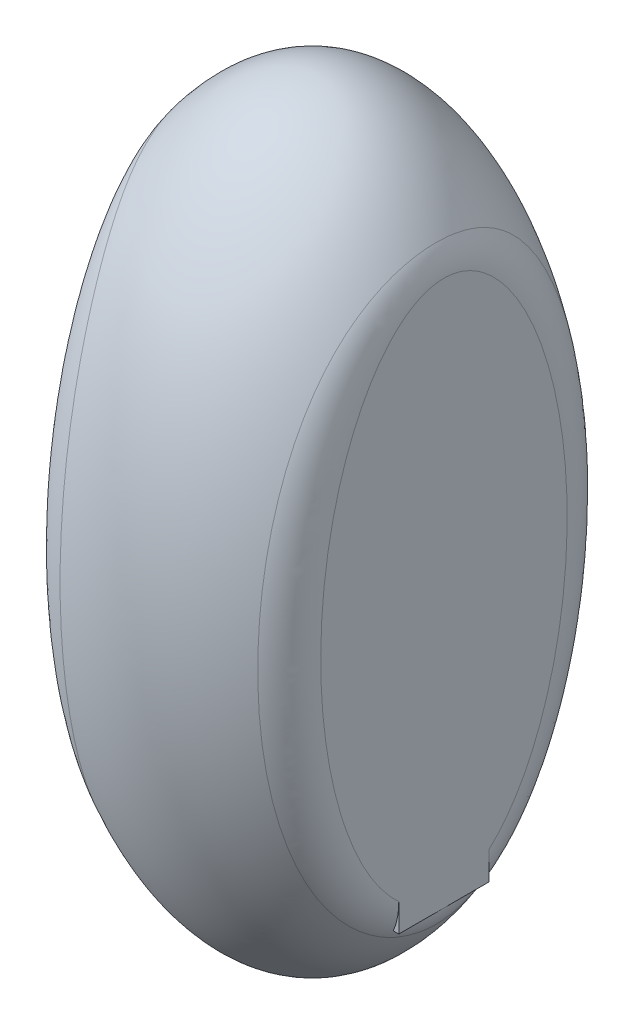
SolidWorks part; units mm, degrees
material "PBT General Purpose"
ref_plane "Front Plane" through (0, 0, 0) normal (0, 0, 1) x (1, 0, 0)
ref_plane "Top Plane" through (0, 0, 0) normal (0, 1, 0) x (1, 0, 0)
ref_plane "Right Plane" through (0, 0, 0) normal (1, 0, 0) x (0, 0, -1)
sketch "Sketch1" plane through (0, 0, 0) normal (0, 0, 1) x (1, 0, 0)
  line L0 (0, 1.15) -> (0, -1.15)
  ellipse E0 centre (0, 0) end of major axis (0, 1.15) minor radius 0.6 (0, -1.15) -> (0, 1.15) ccw
  dimension "D1" = 1.2
  dimension "D2" = 2.3
ref_axis "Axis1" through (0, 1.265, 0) along (0, -1, 0)
revolve "Revolve6" add sketch "Sketch1" angle 360 about L0
sketch "Sketch2" plane through (0, 0, 0) normal (0, 0, 1) x (1, 0, 0)
  line L0 (0, 1.265) -> (0, -1.265) construction
  line L1 (-0.4, 1.1771) -> (-0.895, 1.1771)
  line L2 (-0.4, 1.1771) -> (-0.4, -1.3571)
  line L3 (-0.4, -1.3571) -> (-0.895, -1.3571)
  line L4 (-0.895, 1.1771) -> (-0.895, -1.3571)
  line L5 (0.4, 1.1771) -> (1.03, 1.1771)
  line L6 (0.4, 1.1771) -> (0.4, -1.3571)
  line L7 (0.4, -1.3571) -> (1.03, -1.3571)
  line L8 (1.03, 1.1771) -> (1.03, -1.3571)
  dimension "D1" = 0.4
  dimension "D2" = 0.4
extrude "Cut-Extrude1" cut sketch "Sketch2" against normal through all both and the other way through all
fillet "Fillet1" radius 0.15 1 edges at (0.4, 0.851, -0.0533)
sketch "Sketch3" plane through (0.4, 0, 0) normal (1, 0, 0) x (0, 0, -1)
  line L0 (-0.1371, -0.7554) -> (-0.1371, -0.8413)
  line L1 (-0.1371, -0.8413) -> (0.1371, -0.8413)
  line L2 (0.1371, -0.8413) -> (0.1371, -0.7554)
  line L3 (-0.1371, -0.7554) -> (0.1371, -0.7554)
  spline S0 degree 3 poles (-0.0409, -0.8148) (0.0409, -0.8148) (0.0801, -0.7984) (0.1453, -0.7516) (0.1728, -0.7212) (0.2439, -0.6233) (0.2768, -0.5493) (0.3534, -0.3213) (0.374, -0.1616) (0.3743, 0.1585) (0.3541, 0.3179) (0.2779, 0.5468) (0.2454, 0.6205) (0.1746, 0.7191) (0.1478, 0.7493) (0.0821, 0.7975) (0.0436, 0.8141) (-0.0381, 0.8155) (-0.0774, 0.7998) (-0.1433, 0.7535) (-0.1713, 0.723) (-0.243, 0.6251) (-0.2761, 0.5513) (-0.3533, 0.3223) (-0.374, 0.1605) (-0.3743, -0.1578) (-0.3536, -0.3198) (-0.2776, -0.5475) (-0.2443, -0.6225) (-0.1736, -0.7203) (-0.146, -0.751) (-0.0805, -0.7983) (-0.0409, -0.8148) (0.0409, -0.8148) (0.0801, -0.7984) knots -0.03125 -0.03125 0 0 0.03125 0.03125 0.0625 0.0625 0.125 0.125 0.25 0.25 0.375 0.375 0.4375 0.4375 0.46875 0.46875 0.5 0.5 0.53125 0.53125 0.5625 0.5625 0.625 0.625 0.75 0.75 0.875 0.875 0.9375 0.9375 0.96875 0.96875 1 1 1.03125 1.03125 1.0625 only from (0, -0.8148) to (0, -0.8148) construction
  point P6 (0, -0.8413)
extrude "Boss-Extrude5" add sketch "Sketch3" against normal blind 0.5
fillet "Fillet2" radius 0.3 1 edges at (-0.4, 0.851, 0.0533)
sketch "Sketch4" plane through (-0.4, 0, 0) normal (-1, 0, 0) x (0, 0, 1)
  line L4 (-0.1, -0.3289) -> (0.1, -0.3289)
  line L5 (-0.1, -0.3289) -> (-0.1, -0.3489)
  line L6 (-0.1, -0.3489) -> (0.1, -0.3489)
  line L7 (0.1, -0.3289) -> (0.1, -0.3489)
  point P2 (0, -0.3289)
  dimension "D1" = 0.2
  dimension "D2" = 0.02
extrude "Boss-Extrude6" add sketch "Sketch4" along normal blind 0.01
